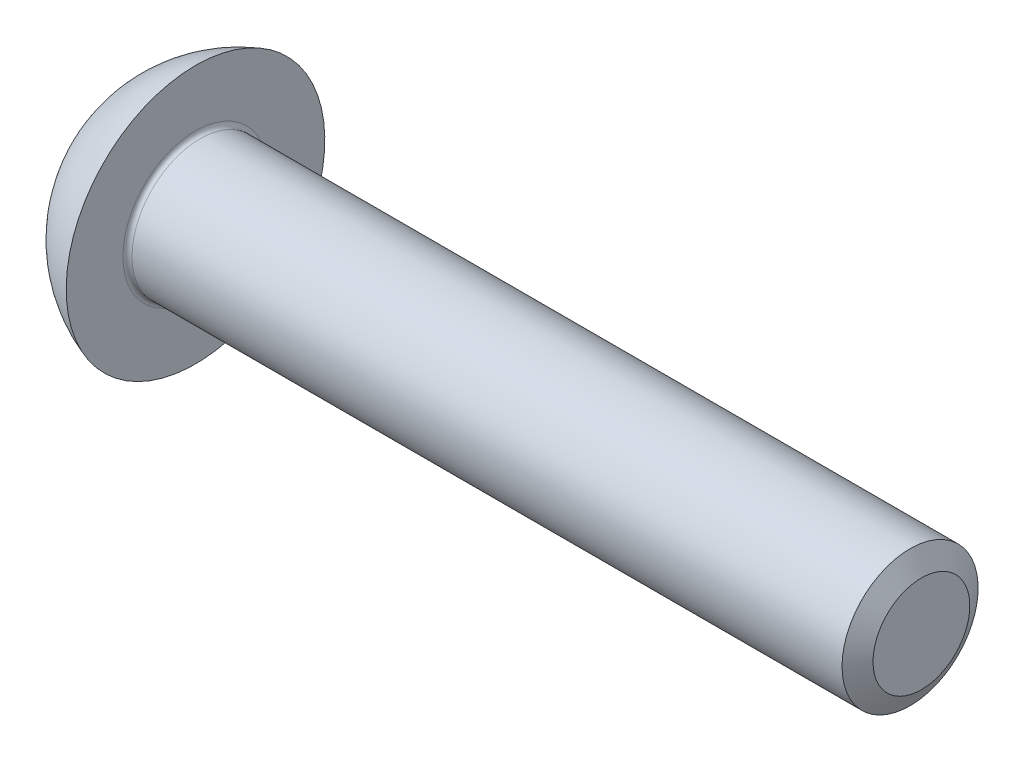
SolidWorks part; units mm, degrees
ref_plane "前视基准面" through (0, 0, 0) normal (0, 0, 1) x (1, 0, 0)
ref_plane "上视基准面" through (0, 0, 0) normal (0, 1, 0) x (1, 0, 0)
ref_plane "右视基准面" through (0, 0, 0) normal (1, 0, 0) x (0, 0, -1)
sketch "尺寸草图" plane through (0, 0, 0) normal (0, 0, 1) x (1, 0, 0)
  line L0 (0, 0) -> (16, 0) construction
  line L1 (16, 0) -> (16, 1.5) construction
  line L2 (16, 1.5) -> (15.5, 1.5) construction
  line L3 (0, 0) -> (0, 2.85) construction
  point P3 (1, 0)
  point P6 (16, 1.8)
  point P7 (0, 0.55)
  point P9 (1.65, 0)
  point P10 (1.75, 0)
  point P11 (16, 1)
  point P12 (2.79, 0)
  point P13 (2.99, 0)
  point P14 (16, 17.8)
  dimension "l" = 16
  dimension "d" = 3
  dimension "P" = 0.5
  dimension "a" = 1
  dimension "da" = 3.6
  dimension "dk" = 5.7
  dimension "e" = 2.3
  dimension "K" = 1.65
  dimension "r" = 0.1
  dimension "s" = 2
  dimension "t" = 1.04
  dimension "w" = 0.2
  dimension "zslwx" = 16
sketch "草图1" plane through (0, 0, 0) normal (0, 0, 1) x (1, 0, 0)
  line L0 (-17.65, 0) -> (0, 0) construction
  line L1 (0, 1.5) -> (-15.9, 1.5)
  line L2 (-16, 1.6) -> (-16, 2.85)
  line L3 (-17.65, 0) -> (-17.65, 1.5)
  line L4 (0, 1.5) -> (0, 0)
  line L5 (-17.65, 0) -> (0, 0)
  arc A0 (-16, 2.85) -> (-17.65, 1.5) centre (-15.0455, 0) ccw
  arc A1 (-15.9, 1.5) -> (-16, 1.6) centre (-15.9, 1.6) cw
  point P10 (-16, 1.5)
  dimension "r" = 0.1
  dimension "d" = 3
  dimension "dk" = 5.7
  dimension "k" = 1.65
  dimension "l" = 16
revolve "旋转1" add sketch "草图1" angle 360 about L0
cosmetic thread "装饰螺纹线1" parameters "D1"=16, "D2"=2.58
sketch "草图2" plane through (-17.65, 0, 0) normal (-1, 0, 0) x (0, 0, 1)
  line L1 (0, 1.1547) -> (-1, 0.5774)
  line L2 (-1, 0.5774) -> (-1, -0.5774)
  line L3 (-1, -0.5774) -> (0, -1.1547)
  line L4 (0, -1.1547) -> (1, -0.5774)
  line L5 (1, -0.5774) -> (1, 0.5774)
  line L6 (1, 0.5774) -> (0, 1.1547)
  circle A0 centre (0, 0) radius 1 construction
  dimension "s" = 2
extrude "切除-拉伸1" cut sketch "草图2" against normal blind 1.65
sketch "草图6" plane through (0, 0, 0) normal (0, 0, 1) x (1, 0, 0)
  line L0 (-16.61, 1.1547) -> (-16, 0)
  line L1 (-15.7, 1.1547) -> (-15.7, 0)
  line L2 (-15.7, 1.1547) -> (-16.61, 1.1547)
  line L3 (-17.65, 0) -> (-16, 0) construction
  line L4 (-15.7, 0) -> (-16, 0)
  line L5 (-17.65, 0) -> (-19.95, 0) construction
  dimension "t" = 1.04
  dimension "e-s" = 0.3
  dimension "k" = 1.65
  dimension "e" = 2.3
revolve "旋转2" add sketch "草图6" angle 360 about L3
sketch "草图7" plane through (0, 0, 0) normal (0, 0, 1) x (1, 0, 0)
  line L3 (-17.65, 1.1547) -> (-17.35, 0)
  line L4 (-17.65, 0) -> (-17.35, 0) construction
  line L7 (-17.65, 1.1547) -> (-17.65, 0)
  line L8 (-17.65, 0) -> (-17.35, 0)
  dimension "e-s" = 0.3
revolve "切除-旋转5" cut sketch "草图7" angle 360 about L4
sketch "草图4" plane through (0, 0, 0) normal (0, 0, 1) x (1, 0, 0)
  line L0 (-0.25, 1.5) -> (0, 1.067)
  line L1 (-0.25, 1.5) -> (0.25, 1.5)
  line L2 (0.25, 1.5) -> (0, 1.067)
  line L4 (0, -1.5) -> (0, 1.5) construction
  line L5 (-0.25, 0) -> (0.25, 0) construction
  dimension "d" = 1.5
  dimension "p" = 0.5
revolve "切除-旋转1" cut sketch "草图4" angle 360 about L5
ref_axis "基准轴1" through (-8.1887, 0, 0) along (1, 0, 0)
pattern_linear "阵列(线性)1" [suppressed] count 30 spacing 0.5 along (-1, 0, 0) of bodies 104
